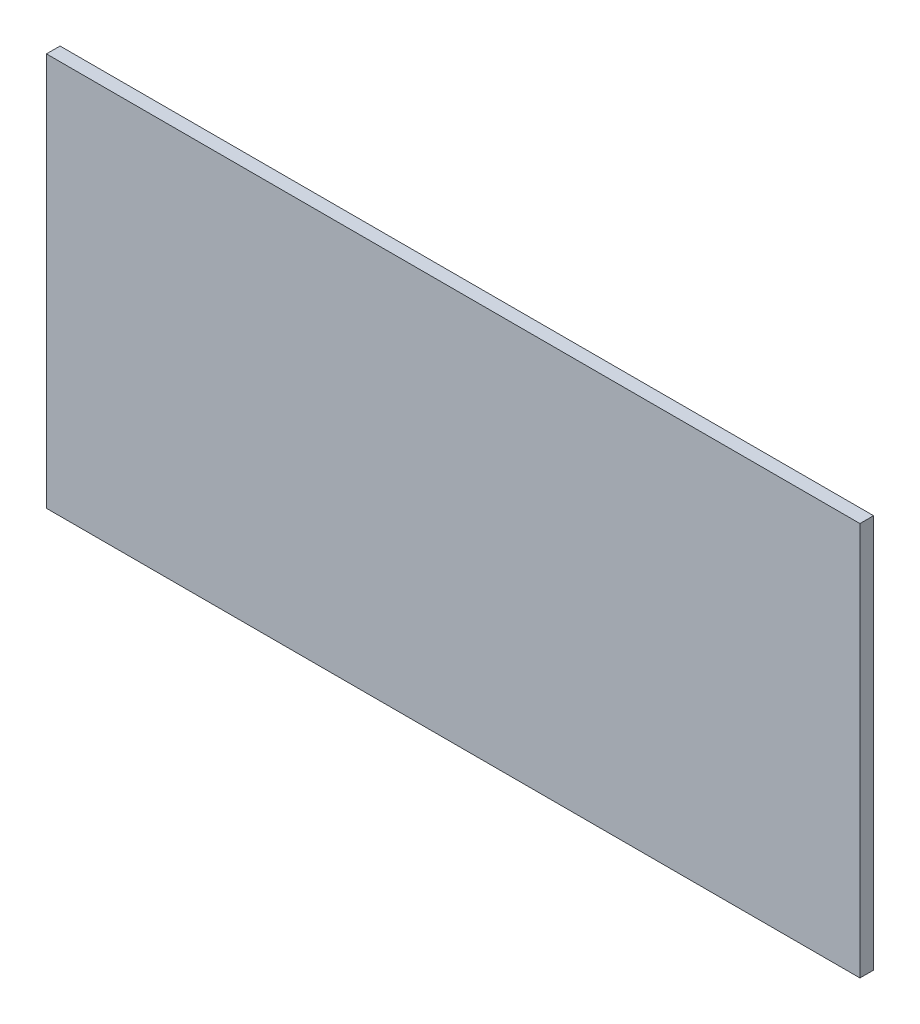
SolidWorks part; units mm, degrees
ref_plane "Front Plane" through (0, 0, 0) normal (0, 0, 1) x (1, 0, 0)
ref_plane "Top Plane" through (0, 0, 0) normal (0, 1, 0) x (1, 0, 0)
ref_plane "Right Plane" through (0, 0, 0) normal (1, 0, 0) x (0, 0, -1)
sketch "Sketch8" plane through (0, 0, 0) normal (0, 0, 1) x (1, 0, 0)
  line L1 (-125.2291, 74.1071) -> (53.8961, 74.1071)
  line L2 (-125.2291, 74.1071) -> (-125.2291, -12.5493)
  line L3 (-125.2291, -12.5493) -> (53.8961, -12.5493)
  line L4 (53.8961, 74.1071) -> (53.8961, -12.5493)
  line L5 (-125.2291, 74.1071) -> (53.8961, -12.5493) construction
  line L6 (-125.2291, -12.5493) -> (53.8961, 74.1071) construction
  point P0 (-35.6665, 30.7789)
base flange "Base-Flange2" sketch "Sketch8" thickness 3 reverse thickness direction no parameters "D1"=0.8
sketch "Sketch14" plane through (-125.2291, 0, 0) normal (-1, 0, 0) x (0, 0, 1)
  line L0 (0, 74.1071) -> (14.6418, 74.1071)
  line L1 (14.6418, 74.1071) -> (14.6418, 79.8506)
sketch "Bend-Lines3" [suppressed] plane through (0, 0, 0) normal (0, 1, 0) x (1, 0, 0)
sketch "Bounding-Box3" [suppressed] plane through (0, 0, 0) normal (0, 1, 0) x (1, 0, 0)
sheet metal parameters "Sheet-Metal2" thickness 3 parameters "D1"=0.8
flat pattern "Flat-Pattern2" [suppressed]
sketch "Bend-Lines4" plane through (0, 0, 0) normal (0, 1, 0) x (1, 0, 0)
sketch3d "Bounding-Box4" [suppressed]
  line L0 (125.2291, -12.5493, 0) -> (-53.8961, -12.5493, 0) construction
  line L1 (125.2291, 74.1071, 0) -> (-53.8961, 74.1071, 0) construction
  line L2 (125.2291, -12.5493, 0) -> (125.2291, 74.1071, 0) construction
  line L3 (-53.8961, -12.5493, 0) -> (-53.8961, 74.1071, 0) construction
